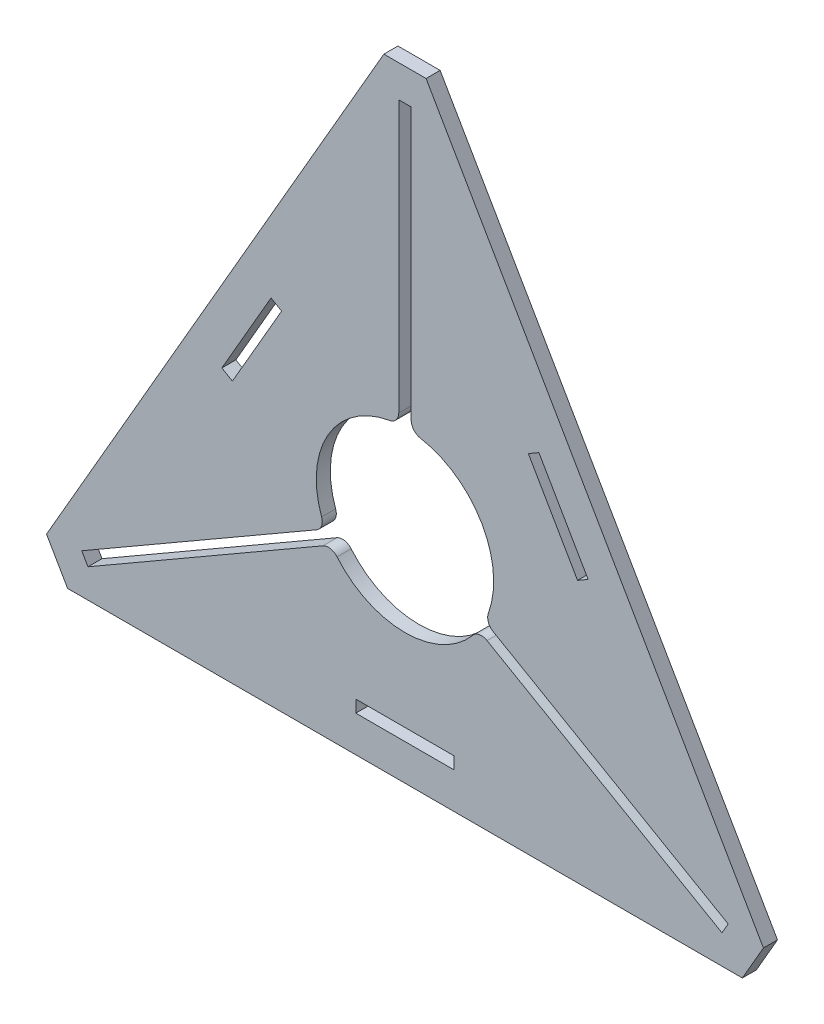
SolidWorks part; units mm, degrees
ref_plane "Front Plane" through (0, 0, 0) normal (0, 0, 1) x (1, 0, 0)
ref_plane "Top Plane" through (0, 0, 0) normal (0, 1, 0) x (1, 0, 0)
ref_plane "Right Plane" through (0, 0, 0) normal (1, 0, 0) x (0, 0, -1)
sketch "Sketch1" plane through (0, 0, 0) normal (0, 0, 1) x (1, 0, 0)
  line L0 (0, 0) -> (0, 146.6407) construction
  line L1 (-2.8067, 166.9701) -> (2.8067, 166.9701)
  line L2 (-2.8067, 166.9701) -> (-2.8067, 44.4543)
  line L4 (2.8067, 166.9701) -> (2.8067, 44.4543)
  line L5 (-2.8067, 166.9701) -> (2.8067, 39.9701) construction
  line L6 (-2.8067, 39.9701) -> (2.8067, 166.9701) construction
  line L7 (146.0037, -81.0544) -> (143.197, -85.9157)
  line L8 (143.197, -85.9157) -> (37.0952, -24.6578)
  line L9 (146.0037, -81.0544) -> (39.9019, -19.7965)
  line L10 (146.0037, -81.0544) -> (33.2118, -22.4157) construction
  line L11 (0, 0) -> (126.9945, -73.3203) construction
  line L12 (36.0185, -17.5544) -> (143.197, -85.9157) construction
  line L13 (-143.197, -85.9157) -> (-146.0037, -81.0544)
  line L14 (-146.0037, -81.0544) -> (-39.9019, -19.7965)
  line L15 (-143.197, -85.9157) -> (-37.0952, -24.6578)
  line L16 (-143.197, -85.9157) -> (-36.0185, -17.5544) construction
  line L17 (0, 0) -> (-126.9945, -73.3203) construction
  line L18 (-33.2118, -22.4157) -> (-146.0037, -81.0544) construction
  line L19 (0, -98.9867) -> (152.4, -98.9867)
  line L21 (0, -98.9867) -> (-152.4, -98.9867)
  line L22 (0, 0) -> (0, -98.9867) construction
  line L23 (-161.925, -82.4889) -> (-9.525, 181.4756)
  line L24 (-9.525, 181.4756) -> (9.525, 181.4756)
  line L25 (-161.925, -82.4889) -> (-152.4, -98.9867)
  line L26 (152.4, -98.9867) -> (161.925, -82.4889)
  line L27 (161.925, -82.4889) -> (9.525, 181.4756)
  line L28 (0, 0) -> (150.3753, 86.8192) construction
  line L29 (-22.225, -77.1808) -> (22.225, -77.1808)
  line L30 (-22.225, -77.1808) -> (-22.225, -82.6926)
  line L31 (-22.225, -82.6926) -> (22.225, -82.6926)
  line L32 (22.225, -77.1808) -> (22.225, -82.6926)
  line L33 (-22.225, -77.1808) -> (22.225, -82.6926) construction
  line L34 (-22.225, -82.6926) -> (22.225, -77.1808) construction
  line L35 (0, 0) -> (-133.6811, 77.1808) construction
  line L36 (-82.7264, 22.0989) -> (-60.5014, 60.5937)
  line L37 (-60.5014, 60.5937) -> (-55.728, 57.8378)
  line L38 (-55.728, 57.8378) -> (-77.953, 19.343)
  line L39 (-77.953, 19.343) -> (-82.7264, 22.0989)
  line L40 (-80.3397, 20.7209) -> (-58.1147, 59.2158) construction
  line L41 (60.5014, 60.5937) -> (55.728, 57.8378)
  line L42 (82.7264, 22.0989) -> (60.5014, 60.5937)
  line L43 (77.953, 19.343) -> (82.7264, 22.0989)
  line L44 (55.728, 57.8378) -> (77.953, 19.343)
  arc A0 (-6.9993, 39.4524) -> (-37.6665, -13.6646) centre (0, 0) ccw
  arc A1 (-30.6672, -25.7878) -> (30.6672, -25.7878) centre (0, 0) ccw
  arc A2 (37.6665, -13.6646) -> (6.9993, 39.4524) centre (0, 0) ccw
  arc A3 (-37.6665, -13.6646) -> (-39.9019, -19.7965) centre (-42.4419, -15.3971) cw
  arc A4 (-37.0952, -24.6578) -> (-30.6672, -25.7878) centre (-34.5552, -29.0572) cw
  arc A5 (30.6672, -25.7878) -> (37.0952, -24.6578) centre (34.5552, -29.0572) cw
  arc A6 (37.6665, -13.6646) -> (39.9019, -19.7965) centre (42.4419, -15.3971) ccw
  arc A7 (6.9993, 39.4524) -> (2.8067, 44.4543) centre (7.8867, 44.4543) cw
  arc A8 (-6.9993, 39.4524) -> (-2.8067, 44.4543) centre (-7.8867, 44.4543) ccw
  point P3 (0, 103.4701)
  point P20 (0, 0)
  point P38 (157.1625, -90.7378)
  point P45 (0, 181.4756)
  point P46 (-157.1625, -90.7378)
  point P47 (0, -79.9367)
  point P52 (-85.725, 49.4934)
  point P55 (85.725, 49.4934)
  point P58 (-66.8405, 38.5904)
  dimension "D1" = 80.137
  dimension "D5" = 5.08
  dimension "D2" = 127
  dimension "D3" = 5.6134
  dimension "D6" = 19.05
  dimension "D7" = 304.8
  dimension "D8" = 152.4
  dimension "D9" = 5.5118
  dimension "D10" = 19.05
  dimension "D11" = 19.05
  dimension "D12" = 44.45
  dimension "D13" = 19.05
  dimension "D14" = 5.5118
  dimension "D15" = 44.45
  dimension "D16" = 19.05
  dimension "D4" = 3
extrude "Boss-Extrude1" add sketch "Sketch1" along normal blind 6.35
